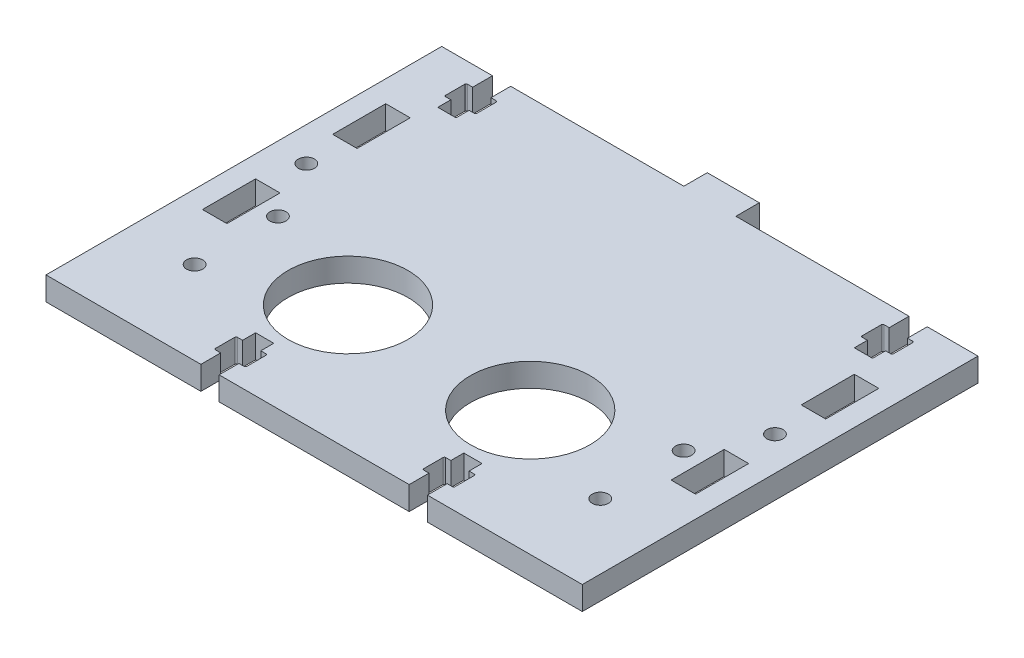
SolidWorks part; units mm, degrees
ref_plane "Front Plane" through (0, 0, 0) normal (0, 0, 1) x (1, 0, 0)
ref_plane "Top Plane" through (0, 0, 0) normal (0, 1, 0) x (1, 0, 0)
ref_plane "Right Plane" through (0, 0, 0) normal (1, 0, 0) x (0, 0, -1)
sketch "Sketch1" plane through (0, 0, 0) normal (0, 1, 0) x (1, 0, 0)
  line L1 (-51.5, 38) -> (51.5, 38)
  line L2 (-51.5, 38) -> (-51.5, -38)
  line L3 (-51.5, -38) -> (51.5, -38)
  line L4 (51.5, 38) -> (51.5, -38)
  line L5 (-51.5, 38) -> (51.5, -38) construction
  line L6 (-51.5, -38) -> (51.5, 38) construction
  point P0 (0, 0)
  dimension "D1" = 103
  dimension "D2" = 76
extrude "MainShape" add sketch "Sketch1" along normal blind 4.5
sketch "Sketch2" plane through (0, 4.5, 0) normal (0, 1, 0) x (1, 0, 0)
  line L0 (0, -38) -> (0, 38) construction
  line L1 (-51.5, -38) -> (51.5, -38) construction
  line L2 (51.5, 38) -> (-51.5, 38) construction
  line L4 (-5, 42.5) -> (5, 42.5)
  line L5 (-5, 42.5) -> (-5, 33.5)
  line L6 (-5, 33.5) -> (5, 33.5)
  line L7 (5, 42.5) -> (5, 33.5)
  line L8 (-5, 42.5) -> (5, 33.5) construction
  line L9 (-5, 33.5) -> (5, 42.5) construction
  dimension "D2" = 4.5
extrude "Tab1" add sketch "Sketch2" against normal through all
sketch "Sketch4" plane through (0, 4.5, 0) normal (0, 1, 0) x (1, 0, 0)
  line L0 (0, 42.5) -> (0, -38) construction
  line L1 (5, 42.5) -> (-5, 42.5) construction
  line L2 (-51.5, -38) -> (51.5, -38) construction
  line L3 (-40, 38) -> (-40, 27.5) construction
  line L4 (-5, 38) -> (-51.5, 38) construction
  line L5 (-38.25, 27.5) -> (-41.75, 27.5) construction
  line L6 (-41.75, 27.5) -> (-41.75, 38) construction
  line L7 (-38.25, 27.5) -> (-41.75, 27.5)
  line L8 (-41.75, 27.5) -> (-41.75, 30)
  line L9 (-41.75, 30) -> (-42.75, 30)
  line L10 (-43, 30.25) -> (-43, 33.95)
  line L11 (-42.75, 34.2) -> (-41.75, 34.2)
  line L12 (-41.75, 34.2) -> (-41.75, 38)
  line L13 (-41.75, 38) -> (-38.25, 38)
  line L14 (-38.25, 27.5) -> (-38.25, 38) construction
  line L15 (-38.25, 34.2) -> (-38.25, 38)
  line L16 (-37.25, 34.2) -> (-38.25, 34.2)
  line L17 (-37, 30.25) -> (-37, 33.95)
  line L18 (-38.25, 30) -> (-37.25, 30)
  line L19 (-38.25, 27.5) -> (-38.25, 30)
  line L20 (38.25, 27.5) -> (38.25, 38) construction
  line L21 (41.75, 27.5) -> (41.75, 38) construction
  line L22 (38.25, 27.5) -> (41.75, 27.5) construction
  line L23 (40, 38) -> (40, 27.5) construction
  line L24 (38.25, 27.5) -> (38.25, 30)
  line L25 (38.25, 30) -> (37.25, 30)
  line L26 (37, 30.25) -> (37, 33.95)
  line L27 (37.25, 34.2) -> (38.25, 34.2)
  line L28 (38.25, 34.2) -> (38.25, 38)
  line L29 (41.75, 38) -> (38.25, 38)
  line L30 (41.75, 34.2) -> (41.75, 38)
  line L31 (42.75, 34.2) -> (41.75, 34.2)
  line L32 (43, 30.25) -> (43, 33.95)
  line L33 (41.75, 30) -> (42.75, 30)
  line L34 (41.75, 27.5) -> (41.75, 30)
  line L35 (38.25, 27.5) -> (41.75, 27.5)
  arc A0 (-42.75, 30) -> (-43, 30.25) centre (-42.75, 30.25) cw
  arc A1 (-37, 30.25) -> (-37.25, 30) centre (-37.25, 30.25) cw
  arc A2 (-37.25, 34.2) -> (-37, 33.95) centre (-37.25, 33.95) cw
  arc A3 (-43, 33.95) -> (-42.75, 34.2) centre (-42.75, 33.95) cw
  arc A4 (43, 33.95) -> (42.75, 34.2) centre (42.75, 33.95) ccw
  arc A5 (37.25, 34.2) -> (37, 33.95) centre (37.25, 33.95) ccw
  arc A6 (37, 30.25) -> (37.25, 30) centre (37.25, 30.25) ccw
  arc A7 (42.75, 30) -> (43, 30.25) centre (42.75, 30.25) ccw
  point P24 (-43, 30)
  point P27 (-37, 30)
  point P30 (-37, 34.2)
  point P33 (-43, 34.2)
  point P56 (43, 34.2)
  point P57 (37, 34.2)
  point P58 (37, 30)
  point P59 (43, 30)
  dimension "D7" = 0.25
  dimension "D1" = 10.5
  dimension "D2" = 1.75
  dimension "D3" = 4.2
  dimension "D4" = 3
  dimension "D5" = 8
  dimension "D6" = 40
extrude "Cut-Extrude2" cut sketch "Sketch4" against normal through all
sketch "Sketch5" plane through (0, 4.5, 0) normal (0, 1, 0) x (1, 0, 0)
  line L0 (0, -38) -> (0, 42.5) construction
  line L1 (-51.5, -38) -> (51.5, -38) construction
  line L2 (5, 42.5) -> (-5, 42.5) construction
  line L3 (45, 38) -> (45, -38) construction
  line L4 (51.5, 38) -> (41.75, 38) construction
  line L5 (-45, 38) -> (-45, -38) construction
  line L6 (42.65, 23.1) -> (47.35, 23.1)
  line L7 (42.65, 23.1) -> (42.65, 12.9)
  line L8 (42.65, 12.9) -> (47.35, 12.9)
  line L9 (47.35, 23.1) -> (47.35, 12.9)
  line L10 (42.65, 23.1) -> (47.35, 12.9) construction
  line L11 (42.65, 12.9) -> (47.35, 23.1) construction
  line L12 (-42.65, 12.9) -> (-47.35, 23.1) construction
  line L13 (-42.65, 23.1) -> (-47.35, 12.9) construction
  line L14 (-47.35, 23.1) -> (-47.35, 12.9)
  line L15 (-42.65, 12.9) -> (-47.35, 12.9)
  line L16 (-42.65, 23.1) -> (-42.65, 12.9)
  line L17 (-42.65, 23.1) -> (-47.35, 23.1)
  line L18 (-51.5, 5.5) -> (51.5, 5.5) construction
  line L19 (-51.5, 38) -> (-51.5, -38) construction
  line L20 (51.5, -38) -> (51.5, 38) construction
  line L21 (-42.65, -12.1) -> (-47.35, -1.9) construction
  line L22 (-42.65, -1.9) -> (-47.35, -12.1) construction
  line L23 (42.65, -1.9) -> (47.35, -12.1) construction
  line L24 (42.65, -12.1) -> (47.35, -1.9) construction
  line L25 (-42.65, -12.1) -> (-47.35, -12.1)
  line L26 (-42.65, -12.1) -> (-42.65, -1.9)
  line L27 (-42.65, -1.9) -> (-47.35, -1.9)
  line L28 (-47.35, -12.1) -> (-47.35, -1.9)
  line L29 (47.35, -12.1) -> (47.35, -1.9)
  line L30 (42.65, -1.9) -> (47.35, -1.9)
  line L31 (42.65, -12.1) -> (42.65, -1.9)
  line L32 (42.65, -12.1) -> (47.35, -12.1)
  line L33 (-42.65, 23.1) -> (-47.35, 12.9) construction
  circle A0 centre (45, 5.5) radius 1.55
  circle A1 centre (-45, 5.5) radius 1.55
  point P10 (45, 18)
  point P21 (-45, 18)
  point P36 (-45, -7)
  point P37 (45, -7)
  dimension "D6" = 3.1
  dimension "D1" = 45
  dimension "D2" = 10.2
  dimension "D3" = 4.7
  dimension "D4" = 20
  dimension "D5" = 25
extrude "Cut-Extrude3" cut sketch "Sketch5" against normal through all
sketch "Sketch6" plane through (0, 4.5, 0) normal (0, 1, 0) x (1, 0, 0)
  line L0 (-17.5, -28) -> (-17.5, 28) construction
  line L2 (5, 42.5) -> (-5, 42.5) construction
  line L3 (-51.5, -14) -> (51.5, -14) construction
  line L4 (-51.5, 38) -> (-51.5, -38) construction
  line L5 (51.5, -38) -> (51.5, 38) construction
  line L6 (51.5, 38) -> (41.75, 38) construction
  line L7 (-51.5, -38) -> (51.5, -38) construction
  line L9 (-51.5, 38) -> (51.5, 38) construction
  circle A0 centre (-17.5, -14) radius 11.5
  point P4 (0, 42.5)
  dimension "D1" = 23
  dimension "D2" = 52
  dimension "D4" = 17.5
extrude "Cut-Extrude4" cut sketch "Sketch6" against normal through all
sketch "Sketch8" plane through (0, 4.5, 0) normal (0, 1, 0) x (1, 0, 0)
  line L0 (-17.5, -2.5) -> (-17.5, -25.5) construction
  line L1 (-17.5, -14) -> (-38.96, -14) construction
  line L2 (-38.96, -22) -> (-38.96, -6) construction
  line L3 (-17.5, -25.5) -> (-17.5, -2.5) construction
  circle A0 centre (-38.96, -6) radius 1.55
  circle A1 centre (-17.5, -14) radius 11.5 construction
  circle A2 centre (-38.96, -22) radius 1.55
  dimension "D3" = 3.1
  dimension "D1" = 0
  dimension "D4" = 21.46
extrude "Cut-Extrude6" cut sketch "Sketch8" against normal through all
sketch "Sketch9" plane through (0, 4.5, 0) normal (0, 1, 0) x (1, 0, 0)
  line L0 (0, -38) -> (0, 42.5) construction
  line L1 (-51.5, -38) -> (51.5, -38) construction
  line L2 (5, 42.5) -> (-5, 42.5) construction
  line L3 (20, -38) -> (20, -27.5) construction
  line L4 (18.25, -27.5) -> (21.75, -27.5) construction
  line L5 (21.75, -27.5) -> (21.75, -38) construction
  line L6 (21.75, -38) -> (21.75, -34.2)
  line L7 (21.75, -34.2) -> (22.75, -34.2)
  line L8 (23, -33.95) -> (23, -30.25)
  line L9 (22.75, -30) -> (21.75, -30)
  line L10 (21.75, -30) -> (21.75, -27.5)
  line L11 (21.75, -27.5) -> (18.25, -27.5)
  line L12 (21.75, -38) -> (18.25, -38)
  line L13 (18.25, -27.5) -> (18.25, -38) construction
  line L14 (18.25, -30) -> (18.25, -27.5)
  line L15 (17.25, -30) -> (18.25, -30)
  line L16 (17, -33.95) -> (17, -30.25)
  line L17 (18.25, -34.2) -> (17.25, -34.2)
  line L18 (18.25, -38) -> (18.25, -34.2)
  line L19 (-18.25, -27.5) -> (-18.25, -38) construction
  line L20 (-21.75, -27.5) -> (-21.75, -38) construction
  line L21 (-18.25, -27.5) -> (-21.75, -27.5) construction
  line L22 (-20, -38) -> (-20, -27.5) construction
  line L23 (-18.25, -38) -> (-18.25, -34.2)
  line L24 (-18.25, -34.2) -> (-17.25, -34.2)
  line L25 (-17, -33.95) -> (-17, -30.25)
  line L26 (-17.25, -30) -> (-18.25, -30)
  line L27 (-18.25, -30) -> (-18.25, -27.5)
  line L28 (-21.75, -38) -> (-18.25, -38)
  line L29 (-21.75, -27.5) -> (-18.25, -27.5)
  line L30 (-21.75, -30) -> (-21.75, -27.5)
  line L31 (-22.75, -30) -> (-21.75, -30)
  line L32 (-23, -33.95) -> (-23, -30.25)
  line L33 (-21.75, -34.2) -> (-22.75, -34.2)
  line L34 (-21.75, -38) -> (-21.75, -34.2)
  arc A0 (22.75, -34.2) -> (23, -33.95) centre (22.75, -33.95) ccw
  arc A1 (23, -30.25) -> (22.75, -30) centre (22.75, -30.25) ccw
  arc A2 (17, -30.25) -> (17.25, -30) centre (17.25, -30.25) cw
  arc A3 (17.25, -34.2) -> (17, -33.95) centre (17.25, -33.95) cw
  arc A4 (-17.25, -34.2) -> (-17, -33.95) centre (-17.25, -33.95) ccw
  arc A5 (-17, -30.25) -> (-17.25, -30) centre (-17.25, -30.25) ccw
  arc A6 (-23, -30.25) -> (-22.75, -30) centre (-22.75, -30.25) cw
  arc A7 (-22.75, -34.2) -> (-23, -33.95) centre (-22.75, -33.95) cw
  point P16 (23, -34.2)
  point P19 (23, -30)
  point P30 (17, -30)
  point P31 (17, -34.2)
  point P54 (-17, -34.2)
  point P55 (-17, -30)
  point P56 (-23, -30)
  point P57 (-23, -34.2)
  dimension "D7" = 0.25
  dimension "D1" = 10.5
  dimension "D2" = 1.75
  dimension "D3" = 8
  dimension "D4" = 4.2
  dimension "D5" = 3
  dimension "D6" = 20
extrude "Cut-Extrude7" cut sketch "Sketch9" against normal through all
sketch "Sketch10" [suppressed] plane through (0, 0, 28) normal (0, 0, 1) x (1, 0, 0)
  line L0 (-55, 2.25) -> (55, 2.25) construction
  line L1 (-55, 4.5) -> (-55, 0) construction
  line L2 (55, 4.5) -> (55, 0) construction
  line L3 (-16, 4.5) -> (-16, 0) construction
  line L4 (-14.25, 4.5) -> (-17.75, 4.5) construction
  line L5 (16, 4.5) -> (16, 0) construction
  line L6 (17.75, 4.5) -> (14.25, 4.5) construction
  line L7 (17.75, 0) -> (14.25, 0) construction
  line L8 (-14.25, 0) -> (-17.75, 0) construction
  circle A0 centre (-16, 2.25) radius 1.6
  circle A1 centre (16, 2.25) radius 1.6
  dimension "D1" = 3.2
  dimension "D2" = 3.2
mirror "Mirror1" about plane through (0, 0, 0) normal (1, 0, 0) of "Cut-Extrude6", "Cut-Extrude4"
equation "\"X-ROD-SPACING\"=45"
equation "\"Y-ROD-SPACING\"=75"
equation "\"Z-ROD-SPACING\"=17.5"
equation "\"Y-BED-OFFSET\"=2"
equation "\"Y-BED-ROD-INSET\"=3.5"
equation "\"Y-BED-SCREW-SPACING\"=209"
equation "\"Y-BED-SCREW-CUTOUT-SLOT-HEIGHT\"=1"
equation "\"T-SLOT-NUT-FILLET-RADIUS\"=0.25"
equation "\"T-SLOT-SCREW-SHAFT-RADIUS\"=1.75"
equation "\"T-SLOT-SCREW-SHAFT-CUTOUT-LENGTH\"=10.5"
equation "\"T-SLOT-NUT-DEPTH\"=4.2"
equation "\"T-SLOT-NUT-WIDTH\"=3"
equation "\"T-SLOT-NUT-END-DISTANCE\"=8"
equation "\"ACRYLIC-THICKNESS\"=10"
equation "\"ACRYLIC-THICKNESS2\"=4.5"
equation "\"ACRYLIC-TAB-CUTOUT-SIZE\"=\"ACRYLIC-THICKNESS\"+\"ACRYLIC-TAB-TOLERANCE\"*2"
equation "\"ACRYLIC-TAB-WIDTH\"=\"ACRYLIC-THICKNESS\""
equation "\"ACRYLIC-M3-HOLE\"=3.1"
equation "\"SMOOTHROD-CAP-SCREW-DISTANCE\"=20"
equation "\"FRAME-WIDTH-INNER\"=370"
equation "\"NEMA17-HOLE-SPACING\"=31"
equation "\"NEMA17-CENTRAL-CUTOUT\"=22.5"
equation "\"Z-BRACKET-REACH\"=55"
equation "\"Z-ROD-INSET\"=16"
equation "\"TOP-BRACKET-SPACING\"=40"
equation "\"SMOOTHROD-X-LENGTH\"=350"
equation "\"SMOOTHROD-Y-LENGTH\"=350"
equation "\"SMOOTHROD-Z-LENGTH\"=350"
equation "\"SMOOTHROD-TIGHTENING-HEADROOM\"=1"
equation "\"LEADSCREW-Z-LENGTH\"=300"
equation "\"SCREW-LENGTH-FRAME\"=\"ACRYLIC-THICKNESS\" + 10"
equation "\"SCREW-LENGTH-MOTOR\"=\"ACRYLIC-THICKNESS\" + 5"
equation "\"SCREW-LENGTH-EXTRUDER\"=28"
equation "\"SCREW-HEAD-RADIUS\"=6"
equation "\"PRINTED-X-SMOOTHROD-DIAMETER\"=8.2"
equation "\"PRINTED-X-SMOOTHROD-CUTOUT\"=10"
equation "\"PRINTED-X-BASE-HEIGHT\"=10"
equation "\"PRINTED-LM8UU-CUTOUT-SIZE\"=15.25"
equation "\"PRINTED-LM8UU-CUTOUT-LENGTH\"=24.5"
equation "\"PRINTED-X-IDLER-HEIGHT\"=16"
equation "\"PSU-MOUNTING-WIDTH\"=95"
equation "\"PSU-MOUNTING-HEIGHT\"=177"
equation "\"Y-BELT-TO-ROD-DISTANCE\"=20"
equation "\"SPOOL-HOLDER-ROD-SPACING\"=150"
equation "\"ACRYLIC-X-CARRIAGE-WIDTH\"=55"
equation "\"ACRYLIC-X-CARRIAGE-HEIGHT\"=75"
equation "\"ACRYLIC-X-CARRIAGE-SCREW-SPACING-X\"=15"
equation "\"ACRYLIC-X-CARRIAGE-SCREW-SPACING-Y\"=33"
equation "\"ACRYLIC-X-CARRIAGE-CENTER-TAB-SPACING\"=14"
equation "\"D1@MainShape\" = \"ACRYLIC-THICKNESS2\""
equation "\"D1@Sketch2\"=\"ACRYLIC-TAB-WIDTH\""
equation "\"D2@Sketch2\"=\"ACRYLIC-THICKNESS2\""
equation "\"D1@Sketch4\"=\"T-SLOT-SCREW-SHAFT-CUTOUT-LENGTH\""
equation "\"D2@Sketch4\"=\"T-SLOT-SCREW-SHAFT-RADIUS\""
equation "\"D3@Sketch4\"=\"T-SLOT-NUT-DEPTH\""
equation "\"D4@Sketch4\"=\"T-SLOT-NUT-WIDTH\""
equation "\"D5@Sketch4\"=\"T-SLOT-NUT-END-DISTANCE\""
equation "\"D7@Sketch4\"=\"T-SLOT-NUT-FILLET-RADIUS\""
equation "\"ACRYLIC-X-CARRIAGE-EXTRUDER-SHELF-DEPTH\"=\"ACRYLIC-X-CARRIAGE-EXTRUDER-OFFSET\" + 30"
equation "\"ACRYLIC-X-CARRIAGE-LM8UU-CUTOUT-WIDTH\"=24.25"
equation "\"ACRYLIC-X-CARRIAGE-EXTRUDER-BRACE-SPACING\"=23"
equation "\"ACRYLIC-X-CARRIAGE-EXTRUDER-BRACE-TAB-OFFSET\"=20"
equation "\"ACRYLIC-X-CARRIAGE-EXTRUDER-BRACE-HEIGHT\"=35"
equation "\"ACRYLIC-X-CARRIAGE-EXTRUDER-BRACE-SCREW-SPACING\"=22"
equation "\"D2@Sketch5\"=\"ACRYLIC-TAB-CUTOUT-SIZE\""
equation "\"D3@Sketch5\"=\"ACRYLIC-THICKNESS2\"+\"ACRYLIC-TAB-TOLERANCE\"*2"
equation "\"D4@Sketch5\"=\"ACRYLIC-X-CARRIAGE-EXTRUDER-BRACE-TAB-OFFSET\""
equation "\"D3@Sketch8\"=\"ACRYLIC-M3-HOLE\""
equation "\"ACRYLIC-X-CARRIAGE-EXTRUDER-ANGLE\"=90"
equation "\"ACRYLIC-X-CARRIAGE-EXTRUDER-OFFSET\"=26"
equation "\"D6@Sketch5\"=\"ACRYLIC-M3-HOLE\""
equation "\"D1@Sketch9\"=\"T-SLOT-SCREW-SHAFT-CUTOUT-LENGTH\""
equation "\"D2@Sketch9\"=\"T-SLOT-SCREW-SHAFT-RADIUS\""
equation "\"D3@Sketch9\"=\"T-SLOT-NUT-END-DISTANCE\""
equation "\"D4@Sketch9\"=\"T-SLOT-NUT-DEPTH\""
equation "\"D5@Sketch9\"=\"T-SLOT-NUT-WIDTH\""
equation "\"D7@Sketch9\"=\"T-SLOT-NUT-FILLET-RADIUS\""
equation "\"ACRYLIC-TAB-TOLERANCE\"=.1"
equation "\"ACRYLIC-X-CARRIAGE-DUAL-WIDTH-MULTIPLIER\"=1.65"
equation "\"ACRYLIC-X-CARRIAGE-DUAL-HOTEND-SPACING\"=42"
equation "\"ACRYLIC-X-CARRIAGE-DUAL-WIDTH\"=103"
equation "\"ACRYLIC-X-CARRIAGE-DUAL-HOTEND-SEPARATION\"=35"
equation "\"ACRYLIC-X-CARRIAGE-DUAL-MOUNT-PLATE-DEPTH\"=76"
equation "\"ACRYLIC-X-CARRIAGE-DUAL-MOUNT-BRACE-WIDTH\"=45"
equation "\"D1@Sketch5\"=\"ACRYLIC-X-CARRIAGE-DUAL-MOUNT-BRACE-WIDTH\""
equation "\"ACRYLIC-X-CARRIAGE-DUAL-MOUNT-SCREW-WIDTH\"=40"
equation "\"D6@Sketch4\"=\"ACRYLIC-X-CARRIAGE-DUAL-MOUNT-SCREW-WIDTH\""
equation "\"D1@Sketch1\"=\"ACRYLIC-X-CARRIAGE-DUAL-WIDTH\""
equation "\"D2@Sketch1\"=\"ACRYLIC-X-CARRIAGE-DUAL-MOUNT-PLATE-DEPTH\""
equation "\"D4@Sketch6\"=\"ACRYLIC-X-CARRIAGE-DUAL-HOTEND-SEPARATION\"/2"
